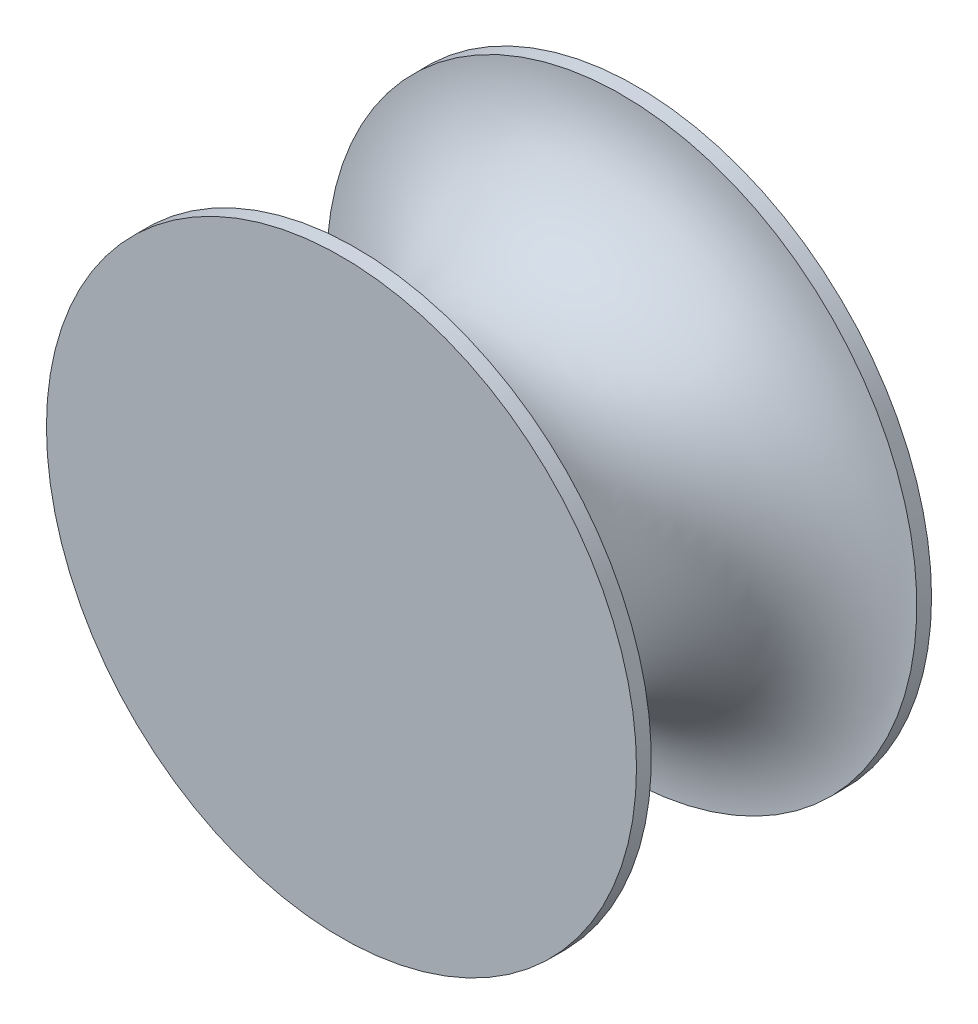
SolidWorks part; units mm, degrees
ref_plane "Front Plane" through (0, 0, 0) normal (0, 0, 1) x (1, 0, 0)
ref_plane "Top Plane" through (0, 0, 0) normal (0, 1, 0) x (1, 0, 0)
ref_plane "Right Plane" through (0, 0, 0) normal (1, 0, 0) x (0, 0, -1)
sketch "Sketch1" plane through (0, 0, 0) normal (0, 0, 1) x (1, 0, 0)
  circle A0 centre (0, 0) radius 12.7
extrude "Boss-Extrude1" add sketch "Sketch1" along normal blind 12.7
sketch "Sketch2" plane through (0, 0, 0) normal (1, 0, 0) x (0, 0, -1)
  line L0 (0, 12.7) -> (-12.7, 12.7) construction
  line L1 (-12.065, 12.7) -> (-0.635, 12.7)
  arc A0 (-12.065, 12.7) -> (-0.635, 12.7) centre (-6.35, 12.7) ccw
revolve "Cut-Revolve1" cut sketch "Sketch2" angle 360 about L0
